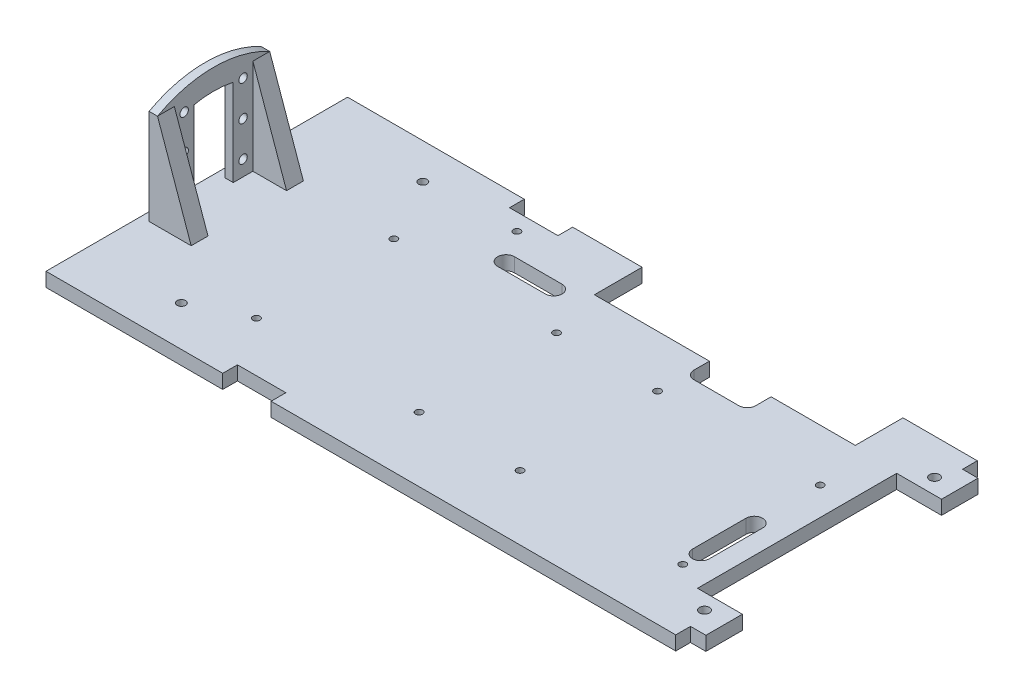
SolidWorks part; units mm, degrees
ref_plane "Front Plane" through (0, 0, 0) normal (0, 0, 1) x (1, 0, 0)
ref_plane "Top Plane" through (0, 0, 0) normal (0, 1, 0) x (1, 0, 0)
ref_plane "Right Plane" through (0, 0, 0) normal (1, 0, 0) x (0, 0, -1)
sketch "Sketch1" plane through (0, 0, 0) normal (0, 1, 0) x (1, 0, 0)
  line L0 (0, 53.75) -> (0, -53.75)
  line L1 (0, -53.75) -> (-230, -53.75)
  line L2 (-230, -53.75) -> (-230, 53.75)
  line L3 (-230, 53.75) -> (0, 53.75)
  point P4 (0, 0)
  dimension "D1" = 230
  dimension "D2" = 107.5
extrude "Main Body" add sketch "Sketch1" along normal mid plane 5
sketch "Sketch6" plane through (0, 0, 0) normal (0, 0, 1) x (1, 0, 0)
  line L0 (-227, 2.5) -> (-227, 36.5)
  line L3 (-212, 2.5) -> (-227, 2.5)
  line L5 (-227, 36.5) -> (-224, 36.5)
  line L6 (-224, 36.5) -> (-212, 2.5)
  line L7 (-230, 2.5) -> (0, 2.5) construction
  line L8 (-230, 2.5) -> (-230, -2.5) construction
  dimension "D1" = 3
  dimension "D2" = 15
  dimension "D3" = 3
  dimension "D4" = 34
extrude "Cam Body" add sketch "Sketch6" along normal mid plane 40
sketch "Sketch7" plane through (0, 36.5, 0) normal (0, 1, 0) x (1, 0, 0)
  line L0 (-227, 7) -> (-227, -7)
  line L1 (-21.45, 0) -> (21.45, 0) construction
  line L2 (-227, -20) -> (-227, 20) construction
  line L3 (-227, -7) -> (-224, -7)
  line L4 (-224, -20) -> (-224, 20) construction
  line L5 (-224, -7) -> (-224, -14)
  line L6 (-224, -14) -> (-212, -14)
  line L7 (-212, -20) -> (-212, 20) construction
  line L8 (-212, -14) -> (-212, 14)
  line L9 (-212, 0) -> (-227, 0) construction
  line L10 (-224, 14) -> (-212, 14)
  line L11 (-224, 7) -> (-224, 14)
  line L12 (-227, 7) -> (-224, 7)
  dimension "D1" = 14
  dimension "D2" = 7
extrude "Cam Slot" cut sketch "Sketch7" against normal up to surface (34 mm away) up to face at (-115, 2.5, 0)
sketch "Sketch8" plane through (-227, 0, 0) normal (-1, 0, 0) x (0, 0, 1)
  line L0 (0, -21.45) -> (0, 21.45) construction
  line L1 (-7, 2.5) -> (-20, 2.5) construction
  circle A0 centre (-10.5, 20.5) radius 1.5
  circle A1 centre (-10.5, 33) radius 1.5
  circle A2 centre (10.5, 33) radius 1.5
  circle A3 centre (10.5, 20.5) radius 1.5
  circle A4 centre (-10.5, 8) radius 1.5
  circle A5 centre (10.5, 8) radius 1.5
  dimension "D3" = 3
  dimension "D4" = 3
  dimension "D6" = 3
  dimension "D1" = 10.5
  dimension "D2" = 12.5
  dimension "D5" = 18
  dimension "D7" = 12.5
extrude "Cam Holes" cut sketch "Sketch8" against normal up to next
sketch "Sketch3" plane through (0, 0, 0) normal (0, 1, 0) x (1, 0, 0)
  line L0 (0, 35.5) -> (0, -35.5)
  line L1 (0, -35.5) -> (-16, -35.5)
  line L2 (-16, -35.5) -> (-16, 35.5)
  line L3 (-16, 35.5) -> (0, 35.5)
  line L4 (-151, 31.25) -> (-134, 31.25) construction
  line L5 (-32, 53.75) -> (-125, 53.75)
  line L6 (-32, 53.75) -> (-32, 36.75)
  line L7 (-32, 36.75) -> (-62, 36.75)
  line L8 (-125, 53.75) -> (-125, 36.75)
  line L9 (-8, 41) -> (-8, -41) construction
  line L10 (-29, -2.25) -> (-23, -2.25) construction
  line L11 (-200, 21.75) -> (-115, 21.75) construction
  line L12 (-200, 21.75) -> (-200, -34.25) construction
  line L13 (-200, -34.25) -> (-115, -34.25) construction
  line L14 (-115, 21.75) -> (-115, -34.25) construction
  line L15 (-178, 18.25) -> (-120, 18.25) construction
  line L16 (-178, 18.25) -> (-178, -30.75) construction
  line L17 (-178, -30.75) -> (-120, -30.75) construction
  line L18 (-120, 18.25) -> (-120, -30.75) construction
  line L19 (-230, 53.75) -> (-230, -53.75) construction
  line L20 (-29, -2.25) -> (-29, -27.25) construction
  line L21 (-29, -27.25) -> (-23, -27.25) construction
  line L22 (-23, -2.25) -> (-23, -27.25) construction
  line L23 (-151, 34.25) -> (-134, 34.25)
  line L24 (-151, 28.25) -> (-134, 28.25)
  line L25 (-26, -5.25) -> (-26, -24.25) construction
  line L26 (-23, -5.25) -> (-23, -24.25)
  line L27 (-29, -5.25) -> (-29, -24.25)
  line L29 (-106, 21.75) -> (-21, 21.75) construction
  line L30 (-106, 21.75) -> (-106, -34.25) construction
  line L31 (-106, -34.25) -> (-21, -34.25) construction
  line L32 (-21, 21.75) -> (-21, -34.25) construction
  line L33 (-84, 18.25) -> (-26, 18.25) construction
  line L34 (-84, 18.25) -> (-84, -30.75) construction
  line L35 (-84, -30.75) -> (-26, -30.75) construction
  line L36 (-26, 18.25) -> (-26, -30.75) construction
  line L37 (0, 53.75) -> (-230, 53.75) construction
  line L38 (0, 53.75) -> (-5.5, 53.75)
  line L39 (0, 53.75) -> (0, 48.5)
  line L40 (0, 48.5) -> (-5.5, 48.5)
  line L41 (-5.5, 53.75) -> (-5.5, 48.5)
  line L42 (0, -53.75) -> (-5.5, -53.75)
  line L43 (0, -53.75) -> (0, -48.5)
  line L44 (0, -48.5) -> (-5.5, -48.5)
  line L45 (-5.5, -53.75) -> (-5.5, -48.5)
  line L47 (-81, 28.25) -> (-65, 28.25)
  line L48 (-84, 31.25) -> (-84, 36.75)
  line L49 (-84, 36.75) -> (-125, 36.75)
  line L50 (-62, 31.25) -> (-62, 36.75)
  circle A0 centre (-8, 41) radius 1.75
  circle A1 centre (-8, -41) radius 1.75
  circle A2 centre (-178, 18.25) radius 1.25
  circle A3 centre (-120, 18.25) radius 1.25
  circle A4 centre (-120, -30.75) radius 1.25
  circle A5 centre (-178, -30.75) radius 1.25
  circle A12 centre (-84, 18.25) radius 1.25
  circle A13 centre (-26, 18.25) radius 1.25
  circle A14 centre (-26, -30.75) radius 1.25
  circle A15 centre (-84, -30.75) radius 1.25
  arc A16 (-151, 34.25) -> (-151, 28.25) centre (-151, 31.25) ccw
  arc A17 (-134, 28.25) -> (-134, 34.25) centre (-134, 31.25) ccw
  arc A18 (-23, -5.25) -> (-29, -5.25) centre (-26, -5.25) ccw
  arc A19 (-29, -24.25) -> (-23, -24.25) centre (-26, -24.25) ccw
  arc A20 (-84, 31.25) -> (-81, 28.25) centre (-81, 31.25) ccw
  arc A21 (-65, 28.25) -> (-62, 31.25) centre (-65, 31.25) ccw
  point P4 (0, 0)
  point P16 (-8, 0)
  point P18 (-8, -35.5)
  point P30 (-200, -6.25)
  point P31 (-178, -6.25)
  point P38 (-142.5, 31.25)
  point P45 (-26, -14.75)
  point P68 (-106, -6.25)
  point P69 (-84, -6.25)
  dimension "D6" = 3.5
  dimension "D7" = 3.5
  dimension "D11" = 2.5
  dimension "D12" = 2.5
  dimension "D13" = 2.5
  dimension "D14" = 2.5
  dimension "D21" = 13
  dimension "D22" = 3.5
  dimension "D23" = 19.5
  dimension "D30" = 5.25
  dimension "D34" = 16
  dimension "D37" = 2.5
  dimension "D38" = 2.5
  dimension "D39" = 2.5
  dimension "D40" = 2.5
  dimension "D27" = 3
  dimension "D28" = 3
  dimension "D24" = 3
  dimension "D43" = 3
  dimension "D1" = 16
  dimension "D2" = 71
  dimension "D3" = 93
  dimension "D4" = 17
  dimension "D5" = 16
  dimension "D8" = 82
  dimension "D9" = 85
  dimension "D10" = 56
  dimension "D15" = 58
  dimension "D16" = 49
  dimension "D17" = 5
  dimension "D18" = 32
  dimension "D19" = 30
  dimension "D20" = 5
  dimension "D25" = 14
  dimension "D26" = 17
  dimension "D29" = 5.5
  dimension "D31" = 5.25
  dimension "D32" = 5.5
  dimension "D35" = 85
  dimension "D36" = 56
  dimension "D41" = 58
  dimension "D42" = 49
  dimension "D44" = 5
extrude "Cut-Extrude2" cut sketch "Sketch3" against normal up to next and the other way through all
sketch "Sketch10" plane through (0, -2.5, 0) normal (0, -1, 0) x (1, 0, 0)
  line L0 (-223.234, -52.4501) -> (-235.3392, 38.75) construction
  line L1 (-235.3392, 38.75) -> (-160, 48.75) construction
  line L2 (-160, 48.75) -> (-147.8947, -42.4501) construction
  line L3 (-147.8947, -42.4501) -> (-223.234, -52.4501) construction
  line L4 (-230, 53.75) -> (-5.5, 53.75) construction
  line L5 (-160, 48.75) -> (-230, 48.75) construction
  line L6 (-160, 48.75) -> (-160, 53.75) construction
  line L7 (-160, 53.75) -> (-230, 53.75) construction
  line L8 (-230, 48.75) -> (-230, 53.75) construction
  line L9 (-167, 53.75) -> (-149.75, 53.75)
  line L10 (-167, 53.75) -> (-167, 48.5)
  line L11 (-167, 48.5) -> (-149.75, 48.5)
  line L12 (-149.75, 53.75) -> (-149.75, 48.5)
  line L13 (-149.75, -53.75) -> (-167, -53.75)
  line L14 (-149.75, -53.75) -> (-149.75, -48.5)
  line L15 (-149.75, -48.5) -> (-167, -48.5)
  line L16 (-167, -53.75) -> (-167, -48.5)
  line L17 (-230, -53.75) -> (-230, 53.75) construction
  line L18 (-125, -53.75) -> (-230, -53.75) construction
  circle A0 centre (-196.0862, 39.4207) radius 1.5
  circle A1 centre (-190.4506, -41.0373) radius 1.5
  circle A2 centre (-158.375, -42.5) radius 1.25
  point P24 (-158.375, -48.5)
  dimension "D8" = 3
  dimension "D11" = 3
  dimension "D17" = 2.5
  dimension "D1" = 76
  dimension "D2" = 92
  dimension "D3" = 5
  dimension "D4" = 70
  dimension "D5" = 10
  dimension "D6" = 39
  dimension "D7" = 4.5
  dimension "D9" = 42
  dimension "D10" = 7
  dimension "D12" = 17.25
  dimension "D13" = 17.25
  dimension "D14" = 5.25
  dimension "D15" = 5.25
  dimension "D16" = 63
  dimension "D18" = 6
  dimension "D19" = 42.5
extrude "Cut-Extrude4" cut sketch "Sketch10" against normal up to next
sketch "Sketch9" plane through (0, -2.5, 0) normal (0, -1, 0) x (-1, 0, 0)
  circle A0 centre (120, 18.25) radius 2.5
  circle A1 centre (178, 18.25) radius 2.5
  circle A2 centre (178, -30.75) radius 2.5
  circle A3 centre (120, -30.75) radius 2.5
  circle A8 centre (158.375, 42.5) radius 2.5
  circle A9 centre (26, 18.25) radius 2.5
  circle A10 centre (84, 18.25) radius 2.5
  circle A11 centre (84, -30.75) radius 2.5
  circle A12 centre (26, -30.75) radius 2.5
  dimension "D1" = 5
  dimension "D2" = 5
  dimension "D3" = 5
  dimension "D4" = 5
  dimension "D5" = 5
  dimension "D6" = 5
  dimension "D7" = 5
  dimension "D9" = 5
  dimension "5" = 5
extrude "Cut-Extrude5" cut sketch "Sketch9" against normal blind 3
sketch "Sketch11" plane through (-227, 0, 0) normal (-1, 0, 0) x (0, 0, 1)
  line L0 (20, 36.5) -> (-20, 36.5) construction
  line L1 (-20, 36.5) -> (-7, 36.5)
  line L2 (-7, 36.5) -> (-7, 33.5)
  line L3 (-7, 2.5) -> (-7, 36.5) construction
  line L4 (20, 36.5) -> (7, 36.5)
  line L5 (7, 36.5) -> (7, 33.5)
  line L6 (7, 2.5) -> (7, 36.5) construction
  arc A0 (20, 36.5) -> (-20, 36.5) centre (0, 0) ccw
  arc A1 (7, 33.5) -> (-7, 33.5) centre (0, 0) ccw
  dimension "D1" = 3
extrude "Boss-Extrude1" add sketch "Sketch11" against normal blind 3
